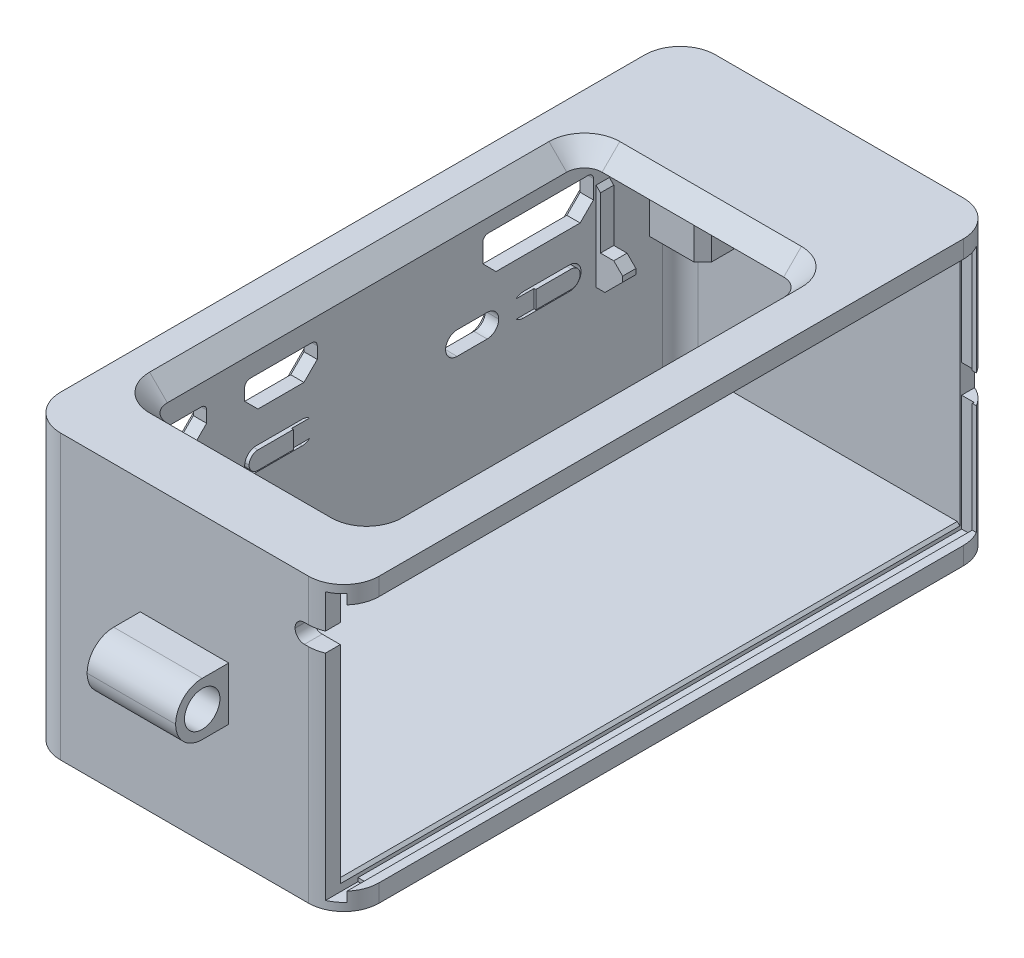
SolidWorks part; units mm, degrees
ref_plane "前视基准面" through (0, 0, 0) normal (0, 0, 1) x (1, 0, 0)
ref_plane "上视基准面" through (0, 0, 0) normal (0, 1, 0) x (1, 0, 0)
ref_plane "右视基准面" through (0, 0, 0) normal (1, 0, 0) x (0, 0, -1)
sketch "草图1" plane through (0, 0, 0) normal (1, 0, 0) x (0, 0, -1)
  line L1 (-54.0501, 29.0398) -> (19.9499, 29.0398)
  line L2 (-54.0501, 29.0398) -> (-54.0501, -2.9602)
  line L3 (-54.0501, -2.9602) -> (19.9499, -2.9602)
  line L4 (19.9499, 29.0398) -> (19.9499, -2.9602)
  dimension "D1" = 74
  dimension "D2" = 32
extrude "凸台-拉伸1" add sketch "草图1" along normal blind 36
sketch "草图2" plane through (36, 0, 0) normal (1, 0, 0) x (0, 0, -1)
  line L8 (17.9499, -0.9602) -> (17.9499, 27.0398)
  line L9 (-52.0501, -0.9602) -> (17.9499, -0.9602)
  line L10 (-52.0501, 27.0398) -> (-52.0501, -0.9602)
  line L11 (17.9499, 27.0398) -> (-52.0501, 27.0398)
  line L12 (17.9499, -0.9602) -> (17.9499, 27.0398)
  line L13 (-52.0501, -0.9602) -> (17.9499, -0.9602)
  line L14 (-52.0501, 27.0398) -> (-52.0501, -0.9602)
  line L15 (17.9499, 27.0398) -> (-52.0501, 27.0398)
  dimension "D1" = 2
extrude "切除-拉伸1" cut sketch "草图2" against normal blind 34
fillet "圆角1" radius 2 2 edges at (2, 13.0398, -17.9499) (2, 13.0398, 52.0501)
fillet "圆角2" radius 4 4 edges at (0, 13.0398, -19.9499) (0, 13.0398, 54.0501) (36, 13.0398, 54.0501) (36, 13.0398, -19.9499)
sketch "草图3" plane through (0, 29.0398, 0) normal (0, 1, 0) x (1, 0, 0)
  line L0 (32, 19.9499) -> (4, 19.9499) construction
  line L1 (29.59, 4.0599) -> (5.07, 4.0599)
  line L2 (29.59, 4.0599) -> (29.59, -45.0601)
  line L3 (29.59, -45.0601) -> (5.07, -45.0601)
  line L4 (5.07, 4.0599) -> (5.07, -45.0601)
  line L5 (36, 15.9499) -> (36, -50.0501) construction
  line L6 (32, -54.0501) -> (4, -54.0501) construction
  line L7 (0, 15.9499) -> (0, -50.0501) construction
  dimension "D1" = 15.89
  dimension "D2" = 6.41
  dimension "D3" = 8.99
  dimension "D4" = 5.07
extrude "切除-拉伸2" cut sketch "草图3" against normal blind 10
fillet "圆角3" radius 2 4 edges at (5.07, 28.0398, 45.0601) (29.59, 28.0398, 45.0601) (29.59, 28.0398, -4.0599) (5.07, 28.0398, -4.0599)
chamfer "倒角1" distance 2 angle 45 8 edges at (17.33, 29.0398, 45.0601) (29.0042, 29.0398, 44.4744) (5.6558, 29.0398, 44.4744) (29.59, 29.0398, 20.5001) (5.07, 29.0398, 20.5001) (29.0042, 29.0398, -3.4741) (5.6558, 29.0398, -3.4741) (17.33, 29.0398, -4.0599)
sketch "草图4" plane through (0, 0, 0) normal (-1, 0, 0) x (0, 0, 1)
  line L0 (-15.9499, 29.0398) -> (50.0501, 29.0398) construction
  line L1 (-8.1499, 22.4398) -> (4.3501, 22.4398)
  line L2 (-8.1499, 22.4398) -> (-8.1499, 18.2398)
  line L3 (-8.1499, 18.2398) -> (4.3501, 18.2398)
  line L4 (4.3501, 22.4398) -> (4.3501, 18.2398)
  line L5 (23.0501, 21.6812) -> (31.2501, 21.6812)
  line L6 (23.0501, 21.6812) -> (23.0501, 18.2398)
  line L7 (23.0501, 18.2398) -> (31.2501, 18.2398)
  line L8 (31.2501, 21.6812) -> (31.2501, 18.2398)
  line L9 (35.5501, 21.6398) -> (43.7501, 21.6398)
  line L10 (35.5501, 21.6398) -> (35.5501, 18.2398)
  line L11 (35.5501, 18.2398) -> (43.7501, 18.2398)
  line L12 (43.7501, 21.6398) -> (43.7501, 18.2398)
  line L13 (-6.7499, 14.7398) -> (1.0501, 14.7398)
  line L14 (-6.7499, 14.7398) -> (-6.7499, 12.1398)
  line L15 (-6.7499, 12.1398) -> (1.0501, 12.1398)
  line L16 (1.0501, 14.7398) -> (1.0501, 12.1398)
  line L17 (23.4501, 14.7398) -> (31.2501, 14.7398)
  line L18 (23.4501, 14.7398) -> (23.4501, 12.1398)
  line L19 (23.4501, 12.1398) -> (31.2501, 12.1398)
  line L20 (31.2501, 14.7398) -> (31.2501, 12.1398)
  line L21 (33.8696, 14.7398) -> (43.3696, 14.7398)
  line L22 (33.8696, 14.7398) -> (33.8696, 11.5398)
  line L23 (33.8696, 11.5398) -> (43.3696, 11.5398)
  line L24 (43.3696, 14.7398) -> (43.3696, 11.5398)
  line L25 (54.0501, 29.0398) -> (54.0501, -2.9602) construction
  line L27 (8.5501, 14.7398) -> (2.5501, 14.7398)
  line L28 (8.5501, 14.7398) -> (8.5501, 12.1398)
  line L29 (8.5501, 12.1398) -> (2.5501, 12.1398)
  line L30 (2.5501, 14.7398) -> (2.5501, 12.1398)
  dimension "D1" = 14.3
  dimension "D2" = 3.2
  dimension "D3" = 2.6
  dimension "D4" = 7.8
  dimension "D5" = 7.8
  dimension "D6" = 8.2
  dimension "D7" = 8.2
  dimension "D8" = 3.4
  dimension "D9" = 12.5
  dimension "D10" = 4.2
  dimension "D11" = 10.8
  dimension "D12" = 10.3
  dimension "D13" = 4.3
  dimension "D14" = 18.7
  dimension "D15" = 9.5
  dimension "D16" = 53
  dimension "D17" = 1.5
  dimension "D18" = 6
extrude "切除-拉伸3" cut sketch "草图4" against normal blind 10
fillet "圆角8" radius 1.3 4 edges at (1, 14.7398, 2.5501) (1, 14.7398, 8.5501) (1, 12.1398, 8.5501) (1, 12.1398, 2.5501)
sketch "草图5" plane through (2, 0, 0) normal (1, 0, 0) x (0, 0, -1)
  line L0 (-23.4501, 12.1398) -> (-23.4501, 14.7398) construction
  line L1 (-23.4501, 14.4398) -> (-30.9501, 14.4398)
  line L2 (-23.4501, 14.4398) -> (-23.4501, 12.4398)
  line L3 (-23.4501, 12.4398) -> (-30.9501, 12.4398)
  line L4 (-30.9501, 14.4398) -> (-30.9501, 12.4398)
  line L5 (-1.0501, 14.7398) -> (-1.0501, 12.1398) construction
  line L6 (-1.0501, 12.4398) -> (6.4499, 12.4398)
  line L7 (-1.0501, 12.4398) -> (-1.0501, 14.4398)
  line L8 (-1.0501, 14.4398) -> (6.4499, 14.4398)
  line L9 (6.4499, 12.4398) -> (6.4499, 14.4398)
  line L10 (-23.4501, 14.7398) -> (-31.2501, 14.7398) construction
  line L11 (-31.2501, 12.1398) -> (-23.4501, 12.1398) construction
  line L12 (-31.2501, 14.7398) -> (-31.2501, 12.1398) construction
  line L13 (6.7499, 14.7398) -> (-1.0501, 14.7398) construction
  line L14 (-1.0501, 12.1398) -> (6.7499, 12.1398) construction
  line L15 (6.7499, 12.1398) -> (6.7499, 14.7398) construction
  dimension "D1" = 0.3
  dimension "D2" = 0.3
  dimension "D3" = 0.3
  dimension "D4" = 0.3
  dimension "D5" = 0.3
  dimension "D6" = 0.3
extrude "凸台-拉伸2" add sketch "草图5" against normal blind 1.2
sketch "草图6" plane through (0.8, 0, 0) normal (-1, 0, 0) x (0, 0, 1)
  line L0 (1.0501, 12.4398) -> (-6.4499, 12.4398) construction
  line L1 (-6.4499, 14.4398) -> (-1.4499, 14.4398)
  line L2 (-6.4499, 14.4398) -> (-6.4499, 12.4398)
  line L3 (-6.4499, 12.4398) -> (-1.4499, 12.4398)
  line L4 (-1.4499, 14.4398) -> (-1.4499, 12.4398)
  line L5 (30.9501, 12.4398) -> (23.4501, 12.4398) construction
  line L6 (30.9501, 14.4398) -> (25.9501, 14.4398)
  line L7 (30.9501, 14.4398) -> (30.9501, 12.4398)
  line L8 (30.9501, 12.4398) -> (25.9501, 12.4398)
  line L9 (25.9501, 14.4398) -> (25.9501, 12.4398)
  dimension "D1" = 5
  dimension "D2" = 5
extrude "凸台-拉伸3" add sketch "草图6" along normal blind 1.5 and the other way blind 1.4
fillet "圆角4" radius 0.6 10 edges at (1, 11.5398, 33.8696) (1, 14.7398, 33.8696) (1, 14.7398, 43.3696) (1, 11.5398, 43.3696) (1, 21.6398, 35.5501) (1, 21.6398, 43.7501) (1, 21.6812, 31.2501) (1, 21.6812, 23.0501) (1, 22.4398, -8.1499) (1, 22.4398, 4.3501)
chamfer "倒角2" distance 1.5 angle 45 6 edges at (1, 18.2398, 43.7501) (1, 18.2398, 35.5501) (1, 18.2398, 31.2501) (1, 18.2398, 23.0501) (1, 18.2398, 4.3501) (1, 18.2398, -8.1499)
fillet "圆角5" radius 1 8 edges at (0.05, 12.4398, 25.9501) (0.05, 14.4398, 25.9501) (0.75, 12.4398, 30.9501) (0.75, 14.4398, 30.9501) (0.05, 12.4398, -1.4499) (0.05, 14.4398, -1.4499) (0.75, 12.4398, -6.4499) (0.75, 14.4398, -6.4499)
chamfer "倒角10" distance 0.2 angle 45 12 edges at (-0.7, 12.4398, 28.4501) (-0.7, 12.7327, 30.6572) (-0.7, 12.7327, 26.243) (-0.7, 14.1469, 30.6572) (-0.7, 14.1469, 26.243) (-0.7, 14.4398, 28.4501) (-0.7, 12.4398, -3.9499) (-0.7, 12.7327, -1.7428) (-0.7, 12.7327, -6.157) (-0.7, 14.1469, -1.7428) (-0.7, 14.1469, -6.157) (-0.7, 14.4398, -3.9499)
fillet "圆角6" radius 1.3 8 edges at (1, 14.7398, 1.0501) (1, 12.1398, 1.0501) (1, 12.1398, -6.7499) (1, 14.7398, -6.7499) (1, 14.7398, 23.4501) (1, 12.1398, 23.4501) (1, 12.1398, 31.2501) (1, 14.7398, 31.2501)
chamfer "倒角4" distance 0.5 angle 45 50 edges at (0, 12.1398, -2.8499) (0, 12.5206, 0.6694) (0, 12.5206, -6.3691) (0, 14.359, 0.6694) (0, 14.359, -6.3691) (0, 14.7398, -2.8499) (0, 18.9898, -7.3999) (0, 18.2398, -1.8999) (0, 18.9898, 3.6001) (0, 20.7898, 4.3501) (0, 20.7898, -8.1499) (0, 22.2641, 4.1744) (0, 22.2641, -7.9741) (0, 22.4398, -1.8999) (0, 11.5398, 38.6196) (0, 11.7155, 43.1938) (0, 11.7155, 34.0453) (0, 13.1398, 43.3696) (0, 13.1398, 33.8696) (0, 14.5641, 43.1938) (0, 14.5641, 34.0453) (0, 14.7398, 38.6196) (0, 12.1398, 27.3501) (0, 12.5206, 30.8694) (0, 12.5206, 23.8309) (0, 14.359, 30.8694) (0, 14.359, 23.8309) (0, 14.7398, 27.3501) (0, 20.4105, 23.0501) (0, 21.5055, 23.2259) (0, 21.6812, 27.1501) (0, 21.5055, 31.0744) (0, 18.9898, 23.8001) (0, 18.2398, 27.1501) (0, 18.9898, 30.5001) (0, 20.4105, 31.2501) (0, 18.9898, 43.0001) (0, 18.2398, 39.6501) (0, 18.9898, 36.3001) (0, 20.3898, 35.5501) (0, 21.4641, 35.7259) (0, 21.6398, 39.6501) (0, 20.3898, 43.7501) (0, 21.4641, 43.5744) (0, 12.5206, 8.1694) (0, 12.1398, 5.5501) (0, 12.5206, 2.9309) (0, 14.359, 8.1694) (0, 14.7398, 5.5501) (0, 14.359, 2.9309)
sketch "草图7" plane through (2, 0, 0) normal (1, 0, 0) x (0, 0, -1)
  line L0 (15.9499, 27.0398) -> (-50.0501, 27.0398) construction
  line L1 (-46.0501, 21.0398) -> (-44.5501, 21.0398)
  line L2 (-46.0501, 21.0398) -> (-46.0501, 11.0398)
  line L3 (-46.0501, 11.0398) -> (-44.5501, 11.0398)
  line L4 (-44.5501, 21.0398) -> (-44.5501, 11.0398)
  line L5 (8.4499, 21.0398) -> (9.9499, 21.0398)
  line L6 (8.4499, 21.0398) -> (8.4499, 11.0398)
  line L7 (8.4499, 11.0398) -> (9.9499, 11.0398)
  line L8 (9.9499, 21.0398) -> (9.9499, 11.0398)
  line L11 (17.9499, -0.9602) -> (17.9499, 27.0398) construction
  line L12 (-52.0501, 27.0398) -> (-52.0501, -0.9602) construction
  dimension "D1" = 6
  dimension "D2" = 10
  dimension "D3" = 1.5
  dimension "D4" = 1.5
  dimension "D5" = 8
  dimension "D6" = 6
extrude "凸台-拉伸4" add sketch "草图7" along normal blind 0.5
sketch "草图10" plane through (2.5, 0, 0) normal (1, 0, 0) x (0, 0, -1)
  line L1 (-46.0501, 11.0398) -> (-44.5501, 11.0398)
  line L2 (-46.0501, 11.0398) -> (-46.0501, 14.6398)
  line L3 (-46.0501, 14.6398) -> (-44.5501, 14.6398)
  line L4 (-44.5501, 11.0398) -> (-44.5501, 14.6398)
  line L7 (8.4499, 11.0398) -> (9.9499, 11.0398)
  line L8 (8.4499, 11.0398) -> (8.4499, 14.6398)
  line L9 (8.4499, 14.6398) -> (9.9499, 14.6398)
  line L10 (9.9499, 11.0398) -> (9.9499, 14.6398)
  dimension "D1" = 3.6
extrude "凸台-拉伸6" add sketch "草图10" along normal blind 2.5
chamfer "倒角7" distance 1 angle 45 2 edges at (5, 14.6398, -9.1999) (5, 14.6398, 45.3001)
chamfer "倒角8" distance 2 angle 45 2 edges at (5, 11.0398, 45.3001) (5, 11.0398, -9.1999)
chamfer "倒角5" distance 0.5 angle 45 2 edges at (2.5, 21.0398, 45.3001) (2.5, 21.0398, -9.1999)
sketch "草图8" plane through (2, 0, 0) normal (1, 0, 0) x (0, 0, -1)
  line L1 (-52.0501, 22.2398) -> (-48.0501, 22.2398)
  line L2 (-52.0501, 22.2398) -> (-52.0501, 24.2398)
  line L3 (-52.0501, 24.2398) -> (-48.0501, 24.2398)
  line L4 (-48.0501, 22.2398) -> (-48.0501, 24.2398)
  line L6 (17.9499, 24.2398) -> (11.9499, 24.2398)
  line L7 (17.9499, 24.2398) -> (17.9499, 22.2398)
  line L8 (17.9499, 22.2398) -> (11.9499, 22.2398)
  line L9 (11.9499, 24.2398) -> (11.9499, 22.2398)
  line L10 (15.9499, 27.0398) -> (-50.0501, 27.0398) construction
  line L11 (17.9499, -0.9602) -> (17.9499, 27.0398) construction
  line L12 (-52.0501, 27.0398) -> (-52.0501, -0.9602) construction
  dimension "D1" = 2.8
  dimension "D2" = 2
  dimension "D3" = 4
  dimension "D4" = 6
extrude "凸台-拉伸5" add sketch "草图8" along normal blind 5
chamfer "倒角6" distance 1 angle 45 2 edges at (7, 24.2398, -14.9499) (7, 24.2398, 50.0501)
sketch "草图12" plane through (0, 0, 54.0501) normal (0, 0, 1) x (1, 0, 0)
  line L0 (4, -0.9602) -> (35.4641, -0.9602) construction
  line L1 (36, 27.0398) -> (33.6, 27.0398)
  line L2 (36, 27.0398) -> (36, -0.9602)
  line L3 (36, -0.9602) -> (33.6, -0.9602)
  line L4 (33.6, 27.0398) -> (33.6, -0.9602)
  dimension "D1" = 2.4
extrude "切除-拉伸5" cut sketch "草图12" against normal blind 10.8
sketch "草图11" plane through (0, -0.9602, 0) normal (0, 1, 0) x (1, 0, 0)
  line L0 (32, 19.9499) -> (4, 19.9499) construction
  line L1 (35, 17.9499) -> (33.6, 17.9499)
  line L2 (35, 17.9499) -> (35, -54.0501)
  line L3 (35, -54.0501) -> (33.6, -54.0501)
  line L4 (33.6, 17.9499) -> (33.6, -54.0501)
  line L5 (32, -54.0501) -> (4, -54.0501) construction
  line L6 (36, -50.0501) -> (36, 15.9499) construction
  dimension "D1" = 2
  dimension "D2" = 0
  dimension "D3" = 1
  dimension "D4" = 1.4
extrude "切除-拉伸4" cut sketch "草图11" against normal blind 0.7
sketch "草图13" plane through (0, 27.0398, 0) normal (0, -1, 0) x (1, 0, 0)
  line L10 (33.6, -17.9499) -> (35, -17.9499)
  line L11 (33.6, 54.0501) -> (33.6, -17.9499)
  line L12 (35, 54.0501) -> (33.6, 54.0501)
  line L13 (35, -17.9499) -> (35, 54.0501)
  line L14 (33.6, -17.9499) -> (35, -17.9499)
  line L15 (33.6, 54.0501) -> (33.6, -17.9499)
  line L16 (35, 54.0501) -> (33.6, 54.0501)
  line L17 (35, -17.9499) -> (35, 54.0501)
  dimension "D1" = 0
extrude "切除-拉伸6" cut sketch "草图13" against normal blind 0.7
sketch "草图14" plane through (0, -1.6602, 0) normal (0, 1, 0) x (1, 0, 0)
  line L1 (33.6, -54.0501) -> (35, -54.0501)
  line L2 (33.6, -54.0501) -> (33.6, -50.0501)
  line L3 (33.6, -50.0501) -> (35, -50.0501)
  line L4 (35, -54.0501) -> (35, -50.0501)
  line L5 (32, -54.0501) -> (4, -54.0501) construction
  line L6 (33.6, -53.7162) -> (33.6, 17.9499) construction
  dimension "D1" = 4
extrude "切除-拉伸7" cut sketch "草图14" against normal blind 0.4
sketch "草图15" plane through (0, 27.7398, 0) normal (0, -1, 0) x (1, 0, 0)
  line L3 (35, 50.0501) -> (35, 52.6959)
  line L4 (33.6, 50.0501) -> (35, 50.0501)
  line L5 (33.6, 53.7162) -> (33.6, 50.0501)
  line L7 (33.6, 50.0501) -> (35, 50.0501)
  line L8 (33.6, 53.7162) -> (33.6, 50.0501)
  line L10 (35, 50.0501) -> (35, 52.6959)
  arc A1 (35, 52.6959) -> (33.6, 53.7162) centre (32, 50.0501) ccw
  arc A2 (35, 52.6959) -> (33.6, 53.7162) centre (32, 50.0501) ccw
  dimension "D1" = 0
extrude "切除-拉伸8" cut sketch "草图15" against normal blind 0.4
sketch "草图16" plane through (0, 0, -17.9499) normal (0, 0, 1) x (1, 0, 0)
  line L0 (33.6, 28.1398) -> (33.6, -2.0602) construction
  line L1 (33.6, 27.7398) -> (35, 27.7398)
  line L2 (33.6, 27.7398) -> (33.6, -1.6602)
  line L3 (33.6, -1.6602) -> (35, -1.6602)
  line L4 (35, 27.7398) -> (35, -1.6602)
extrude "切除-拉伸9" cut sketch "草图16" against normal blind 0.2
chamfer "倒角9" distance 0.3 angle 45 2 edges at (33.6, 27.0398, 17.0501) (33.6, -0.9602, 17.0501)
ref_plane "基准面4" through (0, 13.0398, 0) normal (0, -1, 0) x (-1, 0, 0)
sketch "草图19" plane through (0, 0, -18.1499) normal (0, 0, 1) x (1, 0, 0)
  line L0 (35, 13.0398) -> (40.512, 13.0398) construction
  line L1 (35.4641, -0.9602) -> (35.4641, 27.0398) construction
  line L3 (34.3, 27.7398) -> (34.3, 24.7272) construction
  line L4 (33.6, 27.7398) -> (35, 27.7398) construction
  line L6 (33.6, 14.6398) -> (35.4641, 14.6398)
  line L7 (33.6, 14.6398) -> (33.6, 11.4398)
  line L8 (33.6, 11.4398) -> (35.4641, 11.4398)
  line L9 (35.4641, 14.6398) -> (35.4641, 11.4398)
  line L10 (33.6, 14.6398) -> (35.4641, 11.4398) construction
  line L11 (33.6, 11.4398) -> (35.4641, 14.6398) construction
  point P2 (34.3, 13.0398)
  point P9 (35.4641, 11.1961)
  point P10 (34.5321, 13.0398)
  point P13 (35.4641, 13.0398)
  point P16 (34.3, 27.7398)
  point P17 (35, 14.6366)
  point P18 (0, 0)
  dimension "D1" = 3.2
extrude "切除-拉伸11" cut sketch "草图19" against normal blind 10 and the other way blind 2
sketch "草图20" plane through (0, 0, 54.0501) normal (0, 0, 1) x (1, 0, 0)
  line L0 (33.6, 24.2398) -> (33.6, 28.1198) construction
  line L1 (33.6, 24.2898) -> (30.5, 24.2898)
  line L2 (33.6, 24.2898) -> (33.6, 22.1398)
  line L3 (33.6, 22.1398) -> (30.5, 22.1398)
  line L4 (30.5, 24.2898) -> (30.5, 22.1398)
  line L5 (32, 29.0398) -> (4, 29.0398) construction
  dimension "D1" = 4.75
  dimension "D2" = 2.15
  dimension "D3" = 3.1
extrude "切除-拉伸12" cut sketch "草图20" against normal up to next
fillet "圆角9" radius 1.05 2 edges at (30.5, 24.2898, 53.0501) (30.5, 22.1398, 53.0501)
sketch "草图21" plane through (0, 0, -19.9499) normal (0, 0, -1) x (-1, 0, 0)
  line L0 (-25, 19.5398) -> (-14, 19.5398) construction
  line L1 (-25, 21.0398) -> (-14, 21.0398)
  line L2 (-25, 18.0398) -> (-14, 18.0398)
  line L3 (-4, -2.9602) -> (-4, 29.0398) construction
  line L4 (-32, 29.0398) -> (-4, 29.0398) construction
  arc A0 (-25, 21.0398) -> (-25, 18.0398) centre (-25, 19.5398) ccw
  arc A1 (-14, 18.0398) -> (-14, 21.0398) centre (-14, 19.5398) ccw
  point P2 (-19.5, 19.5398)
  dimension "D4" = 1.5
  dimension "D1" = 10
  dimension "D2" = 9.5
  dimension "D3" = 11
extrude "切除-拉伸13" cut sketch "草图21" against normal up to next
sketch "草图22" plane through (0, -2.9602, 0) normal (0, -1, 0) x (1, 0, 0)
  line L0 (7.07, -6.0599) -> (27.59, -6.0599) construction
  line B0 (12.438, 7.4573) -> (11.965, 6.6368)
  line B1 (11.965, 6.6368) -> (9.5089, 2.3799)
  line B2 (9.5089, 2.3799) -> (9.0302, 1.5593)
  line B3 (9.0302, -0.1617) -> (9.5089, -0.9823)
  line B4 (9.5089, -0.9823) -> (11.965, -5.2392)
  line B5 (11.965, -5.2392) -> (12.438, -6.0599)
  line B6 (13.9253, -6.9204) -> (20.7409, -6.9204)
  line B7 (22.2283, -6.0599) -> (22.7013, -5.2392)
  line B8 (22.7013, -5.2392) -> (25.1574, -0.9823)
  line B9 (25.1574, -0.9823) -> (25.6361, -0.1617)
  line B10 (25.6361, 1.5593) -> (25.1574, 2.3799)
  line B11 (25.1574, 2.3799) -> (22.7013, 6.6368)
  line B12 (22.7013, 6.6368) -> (22.2283, 7.4573)
  line B13 (20.7409, 8.3178) -> (13.9253, 8.3178)
  line B14 (13.1161, -4.9657) -> (10.073, 0.2999)
  line B15 (10.073, 1.1034) -> (13.1218, 6.3404)
  line B16 (13.8228, 6.3461) -> (16.8658, 1.2573)
  line B17 (22.0231, 2.8358) -> (22.3536, 2.2431)
  line B18 (22.4505, 2.1861) -> (24.1601, 2.1861)
  line B19 (24.257, 2.1292) -> (24.8838, 1.0236)
  line B20 (24.787, 0.8583) -> (19.51, 0.8583)
  line B21 (19.4131, 0.9153) -> (18.3475, 2.7959)
  line B22 (21.6698, 6.7393) -> (22.291, 5.6452)
  line B23 (22.1941, 5.4799) -> (19.681, 5.4799)
  line B24 (19.5841, 5.537) -> (18.9686, 6.6311)
  line B25 (19.0655, 6.7963) -> (21.5729, 6.7963)
  line B26 (21.0088, 2.7674) -> (21.2709, 2.2431)
  line B27 (21.1512, 2.1861) -> (19.8064, 2.1861)
  line B28 (19.7095, 2.2431) -> (19.4359, 2.7332)
  line B29 (14.404, 12.3126) -> (14.404, 10.4377)
  line B30 (14.404, 10.4377) -> (20.9689, 10.4377)
  line B31 (20.9689, 10.4377) -> (20.9689, 11.2698)
  line B32 (20.9689, 11.2698) -> (18.3646, 11.2698)
  line B33 (18.3646, 11.2698) -> (18.3646, 12.3582)
  line B34 (17.6921, 12.25) -> (17.6921, 11.2698)
  line B35 (17.6921, 11.2698) -> (15.0765, 11.2698)
  line B36 (15.0765, 11.2698) -> (15.0765, 12.2158)
  line B37 (16.1022, 15.8514) -> (20.9689, 15.8514)
  line B38 (20.9689, 15.8514) -> (20.9689, 16.6665)
  line B39 (20.9689, 16.6665) -> (16.1022, 16.6665)
  line B40 (16.1022, 16.6665) -> (16.1022, 15.8514)
  line B41 (17.1793, 21.3735) -> (16.8487, 20.5415)
  line B42 (16.0623, 21.6983) -> (15.0594, 22.4962)
  line B43 (18.0227, 19.265) -> (18.3817, 20.1141)
  line B44 (19.0313, 18.564) -> (20.1369, 17.658)
  line B45 (15.8743, 26.4795) -> (19.2137, 26.4795)
  line B46 (18.8262, 25.0377) -> (15.8743, 25.0377)
  line B47 (15.8743, 25.0377) -> (15.8743, 23.4478)
  line B48 (15.8743, 23.4478) -> (19.0256, 23.4478)
  line B49 (20.2679, 26.6277) -> (20.2679, 26.6618)
  line B50 (20.2679, 26.6618) -> (20.9689, 26.7759)
  line B51 (20.9689, 26.7759) -> (20.9689, 28.0751)
  line B52 (20.9689, 28.0751) -> (15.8743, 28.0751)
  line B53 (15.8743, 28.0751) -> (15.8743, 26.4795)
  line B54 (19.9659, 31.9274) -> (19.9659, 31.1239)
  line B55 (17.0254, 33.0216) -> (17.0254, 33.8079)
  line B56 (17.0254, 33.8079) -> (15.8743, 33.8079)
  line B57 (15.8743, 33.8079) -> (15.8743, 31.9388)
  line B58 (18.9174, 29.6878) -> (18.9516, 29.6878)
  line B59 (20.7808, 29.591) -> (20.8264, 29.591)
  line B60 (21.1854, 31.141) -> (21.1854, 31.6254)
  line B61 (16.4156, 34.2638) -> (17.4642, 34.8223)
  line B62 (20.456, 37.0676) -> (20.456, 37.1075)
  line B63 (20.456, 37.1075) -> (20.9689, 37.2214)
  line B64 (20.9689, 37.2214) -> (20.9689, 38.5207)
  line B65 (20.9689, 38.5207) -> (18.074, 38.5207)
  line B66 (18.6381, 36.9251) -> (19.453, 36.9251)
  line B67 (16.7576, 41.0111) -> (16.7576, 40.9769)
  line B68 (16.7576, 40.9769) -> (15.8743, 40.8686)
  line B69 (15.8743, 40.8686) -> (15.8743, 39.5693)
  line B70 (15.8743, 39.5693) -> (20.9689, 39.5693)
  line B71 (20.9689, 39.5693) -> (20.9689, 41.1536)
  line B72 (20.9689, 41.1536) -> (18.0569, 41.1536)
  line B73 (17.2248, 42.8118) -> (15.8515, 43.0796)
  line B74 (21.2709, 2.2431) -> (22.3536, 2.2431)
  line B75 (21.1512, 2.1861) -> (22.4505, 2.1861)
  spline B76 degree 3 poles (9.0302, 1.5593) (8.882, 1.2914) (8.8022, 0.9951) (8.8022, 0.6988) knots 3 3 3 3 4 4 4 4
  spline B77 degree 3 poles (8.8022, 0.6988) (8.8022, 0.4025) (8.882, 0.1061) (9.0302, -0.1617) knots 4 4 4 4 5 5 5 5
  spline B78 degree 3 poles (12.438, -6.0599) (12.7457, -6.5898) (13.3156, -6.9204) (13.9253, -6.9204) knots 8 8 8 8 9 9 9 9
  spline B79 degree 3 poles (20.7409, -6.9204) (21.3564, -6.9204) (21.9206, -6.5898) (22.2283, -6.0599) knots 10 10 10 10 11 11 11 11
  spline B80 degree 3 poles (25.6361, -0.1617) (25.7899, 0.1061) (25.864, 0.4025) (25.864, 0.6988) knots 14 14 14 14 15 15 15 15
  spline B81 degree 3 poles (25.864, 0.6988) (25.864, 0.9951) (25.7899, 1.2914) (25.6361, 1.5593) knots 15 15 15 15 16 16 16 16
  spline B82 degree 3 poles (22.2283, 7.4573) (21.9206, 7.993) (21.3564, 8.3178) (20.7409, 8.3178) knots 19 19 19 19 20 20 20 20
  spline B83 degree 3 poles (13.9253, 8.3178) (13.3156, 8.3178) (12.7457, 7.993) (12.438, 7.4573) knots 21 21 21 21 22 22 22 22
  spline B84 degree 2 poles (16.8658, 0.146) (13.8911, -5.0056) (13.8854, -5.017) knots 0 0 0 1 1 1
  spline B85 degree 3 poles (13.8854, -5.017) (13.6917, -5.2848) (13.2814, -5.2563) (13.1161, -4.9657) knots 1 1 1 1 2 2 2 2
  spline B86 degree 3 poles (10.073, 0.2999) (9.9306, 0.5449) (9.9306, 0.8527) (10.073, 1.1034) knots 3 3 3 3 4 4 4 4
  spline B87 degree 3 poles (13.1218, 6.3404) (13.2757, 6.6082) (13.6632, 6.6139) (13.8228, 6.3461) knots 5 5 5 5 6 6 6 6
  spline B88 degree 3 poles (16.8658, 1.2573) (17.0653, 0.9153) (17.0653, 0.4879) (16.8658, 0.146) knots 7 7 7 7 8 8 8 8
  spline B89 degree 3 poles (24.1601, 2.1861) (24.2, 2.1861) (24.2342, 2.169) (24.257, 2.1292) knots 3 3 3 3 4 4 4 4
  spline B90 degree 3 poles (24.8838, 1.0236) (24.9237, 0.9495) (24.8725, 0.8583) (24.787, 0.8583) knots 5 5 5 5 6 6 6 6
  spline B91 degree 3 poles (19.51, 0.8583) (19.4701, 0.8583) (19.4302, 0.8754) (19.4131, 0.9153) knots 7 7 7 7 8 8 8 8
  spline B92 degree 3 poles (18.3475, 2.7959) (17.6579, 4.0154) (17.5212, 5.024) (18.8889, 5.024) knots 9 9 9 9 10 10 10 10
  spline B93 degree 3 poles (18.8889, 5.024) (20.2053, 5.024) (21.3621, 4.004) (22.0231, 2.8358) knots 10 10 10 10 11 11 11 11
  spline B94 degree 3 poles (21.5729, 6.7963) (21.6128, 6.7963) (21.6527, 6.7735) (21.6698, 6.7393) knots 0 0 0 0 1 1 1 1
  spline B95 degree 3 poles (22.291, 5.6452) (22.3309, 5.5711) (22.2795, 5.4799) (22.1941, 5.4799) knots 2 2 2 2 3 3 3 3
  spline B96 degree 3 poles (19.681, 5.4799) (19.6411, 5.4799) (19.6069, 5.5027) (19.5841, 5.537) knots 4 4 4 4 5 5 5 5
  spline B97 degree 3 poles (18.9686, 6.6311) (18.9288, 6.7051) (18.98, 6.7963) (19.0655, 6.7963) knots 6 6 6 6 7 7 7 7
  spline B98 degree 3 poles (17.2989, 6.141) (17.0482, 6.5798) (17.1565, 6.8932) (17.5554, 6.8932) (17.9486, 6.8932) (18.4102, 6.5798) (18.6552, 6.141) knots 2 2 2 2 3 3 3 4 4 4 4
  spline B99 degree 3 poles (18.6552, 6.141) (18.9117, 5.6965) (18.8034, 5.3831) (18.4102, 5.3831) (18.0056, 5.3831) (17.5497, 5.6965) (17.2989, 6.141) knots 0 0 0 0 1 1 1 2 2 2 2
  spline B100 degree 3 poles (19.624, 3.7248) (20.1654, 3.7248) (20.644, 3.4171) (21.0088, 2.7674) knots 0 0 0 0 1 1 1 1
  spline B101 degree 3 poles (19.8064, 2.1861) (19.7665, 2.1861) (19.7266, 2.2089) (19.7095, 2.2431) knots 4 4 4 4 5 5 5 5
  spline B102 degree 3 poles (19.4359, 2.7332) (19.0712, 3.3714) (19.0655, 3.7248) (19.624, 3.7248) knots 6 6 6 6 7 7 7 7
  spline B103 degree 3 poles (18.3646, 12.3582) (18.3646, 13.7886) (17.715, 14.7745) (16.3302, 14.7745) knots 5 5 5 5 6 6 6 6
  spline B104 degree 3 poles (16.3302, 14.7745) (14.8941, 14.7745) (14.404, 13.7886) (14.404, 12.3126) knots 6 6 6 6 7 7 7 7
  spline B105 degree 3 poles (15.0765, 12.2158) (15.0765, 13.3669) (15.3785, 13.9482) (16.3302, 13.9482) knots 3 3 3 3 4 4 4 4
  spline B106 degree 3 poles (16.3302, 13.9482) (17.2704, 13.9482) (17.6921, 13.4068) (17.6921, 12.25) knots 4 4 4 4 5 5 5 5
  spline B107 degree 3 poles (15.0993, 16.2618) (15.0993, 16.5866) (14.877, 16.826) (14.575, 16.826) (14.2388, 16.826) (14.045, 16.5866) (14.045, 16.2618) knots 2 2 2 2 3 3 3 4 4 4 4
  spline B108 degree 3 poles (14.045, 16.2618) (14.045, 15.937) (14.2388, 15.6976) (14.575, 15.6976) (14.877, 15.6976) (15.0993, 15.937) (15.0993, 16.2618) knots 0 0 0 0 1 1 1 2 2 2 2
  spline B109 degree 3 poles (16.8487, 20.5415) (16.6151, 19.9545) (16.4726, 19.5328) (16.1022, 19.5328) knots 1 1 1 1 2 2 2 2
  spline B110 degree 3 poles (16.1022, 19.5328) (15.7489, 19.5328) (15.5494, 19.8349) (15.5494, 20.3306) knots 2 2 2 2 3 3 3 3
  spline B111 degree 3 poles (15.5494, 20.3306) (15.5494, 20.8492) (15.7261, 21.2595) (16.0623, 21.6983) knots 3 3 3 3 4 4 4 4
  spline B112 degree 3 poles (15.0594, 22.4962) (14.4724, 21.9149) (14.1761, 21.1) (14.1761, 20.3306) knots 5 5 5 5 6 6 6 6
  spline B113 degree 3 poles (14.1761, 20.3306) (14.1761, 18.9117) (15.0765, 17.9087) (16.1934, 17.9087) knots 6 6 6 6 7 7 7 7
  spline B114 degree 3 poles (16.1934, 17.9087) (17.1622, 17.9087) (17.7434, 18.564) (18.0227, 19.265) knots 7 7 7 7 8 8 8 8
  spline B115 degree 3 poles (18.3817, 20.1141) (18.621, 20.684) (18.7464, 21.0544) (19.1339, 21.0544) knots 9 9 9 9 10 10 10 10
  spline B116 degree 3 poles (19.1339, 21.0544) (19.4929, 21.0544) (19.7152, 20.7752) (19.7152, 20.1825) knots 10 10 10 10 11 11 11 11
  spline B117 degree 3 poles (19.7152, 20.1825) (19.7152, 19.6582) (19.4359, 19.037) (19.0313, 18.564) knots 11 11 11 11 12 12 12 12
  spline B118 degree 3 poles (20.1369, 17.658) (20.7694, 18.3475) (21.0943, 19.282) (21.0943, 20.1483) knots 13 13 13 13 14 14 14 14
  spline B119 degree 3 poles (21.0943, 20.1483) (21.0943, 21.761) (20.1198, 22.6955) (19.0085, 22.6955) knots 14 14 14 14 15 15 15 15
  spline B120 degree 3 poles (19.0085, 22.6955) (18.0683, 22.6955) (17.5098, 22.1998) (17.1793, 21.3735) knots 15 15 15 15 16 16 16 16
  spline B121 degree 3 poles (19.2137, 26.4795) (19.5898, 26.2117) (19.7323, 25.9894) (19.7323, 25.6304) knots 1 1 1 1 2 2 2 2
  spline B122 degree 3 poles (19.7323, 25.6304) (19.7323, 25.2258) (19.5328, 25.0377) (18.8262, 25.0377) knots 2 2 2 2 3 3 3 3
  spline B123 degree 3 poles (19.0256, 23.4478) (20.2964, 23.4478) (21.0943, 23.9208) (21.0943, 25.032) knots 6 6 6 6 7 7 7 7
  spline B124 degree 3 poles (21.0943, 25.032) (21.0943, 25.7273) (20.7694, 26.206) (20.2679, 26.6277) knots 7 7 7 7 8 8 8 8
  spline B125 degree 3 poles (19.9659, 31.1239) (19.9659, 30.5768) (19.8576, 30.3717) (19.624, 30.3717) knots 1 1 1 1 2 2 2 2
  spline B126 degree 3 poles (19.624, 30.3717) (19.453, 30.3717) (19.3732, 30.4115) (19.265, 30.5312) knots 2 2 2 2 3 3 3 3
  spline B127 degree 3 poles (19.265, 30.5312) (19.3276, 30.7535) (19.3562, 30.9586) (19.3562, 31.1296) knots 3 3 3 3 4 4 4 4
  spline B128 degree 3 poles (19.3562, 31.1296) (19.3562, 32.2579) (18.8376, 33.164) (17.6466, 33.164) knots 4 4 4 4 5 5 5 5
  spline B129 degree 3 poles (17.6466, 33.164) (17.4015, 33.164) (17.1679, 33.1013) (17.0254, 33.0216) knots 5 5 5 5 6 6 6 6
  spline B130 degree 3 poles (15.8743, 31.9388) (15.7888, 31.7051) (15.7489, 31.4259) (15.7489, 31.1296) knots 9 9 9 9 10 10 10 10
  spline B131 degree 3 poles (15.7489, 31.1296) (15.7489, 30.0298) (16.353, 28.9983) (17.601, 28.9983) knots 10 10 10 10 11 11 11 11
  spline B132 degree 3 poles (17.601, 28.9983) (18.1936, 28.9983) (18.6666, 29.3288) (18.9174, 29.6878) knots 11 11 11 11 12 12 12 12
  spline B133 degree 3 poles (18.9516, 29.6878) (19.1852, 29.3573) (19.5442, 29.1236) (19.9032, 29.1236) knots 13 13 13 13 14 14 14 14
  spline B134 degree 3 poles (19.9032, 29.1236) (20.3306, 29.1236) (20.5985, 29.3231) (20.7808, 29.591) knots 14 14 14 14 15 15 15 15
  spline B135 degree 3 poles (20.8264, 29.591) (21.0658, 29.1179) (21.4077, 28.8672) (21.8294, 28.8672) knots 16 16 16 16 17 17 17 17
  spline B136 degree 3 poles (21.8294, 28.8672) (22.7411, 28.8672) (23.1116, 29.8303) (23.1116, 31.0042) knots 17 17 17 17 18 18 18 18
  spline B137 degree 3 poles (23.1116, 31.0042) (23.1116, 32.7765) (22.348, 33.8878) (21.2709, 33.8878) knots 18 18 18 18 19 19 19 19
  spline B138 degree 3 poles (21.2709, 33.8878) (20.3477, 33.8878) (19.9659, 33.1811) (19.9659, 31.9274) knots 19 19 19 19 20 20 20 20
  spline B139 degree 3 poles (18.3988, 31.1296) (18.3988, 30.7649) (18.1309, 30.4857) (17.601, 30.4857) (17.0824, 30.4857) (16.8146, 30.7649) (16.8146, 31.1296) knots 2 2 2 2 3 3 3 4 4 4 4
  spline B140 degree 3 poles (16.8146, 31.1296) (16.8146, 31.5057) (17.0824, 31.7735) (17.601, 31.7735) (18.1309, 31.7735) (18.3988, 31.5057) (18.3988, 31.1296) knots 0 0 0 0 1 1 1 2 2 2 2
  spline B141 degree 3 poles (22.1143, 31.2549) (22.1143, 30.5996) (21.9376, 30.1722) (21.5786, 30.1722) knots 0 0 0 0 1 1 1 1
  spline B142 degree 3 poles (21.5786, 30.1722) (21.4077, 30.1722) (21.2652, 30.252) (21.1227, 30.4115) knots 1 1 1 1 2 2 2 2
  spline B143 degree 3 poles (21.1227, 30.4115) (21.1683, 30.5768) (21.1854, 30.7706) (21.1854, 31.141) knots 2 2 2 2 3 3 3 3
  spline B144 degree 3 poles (21.1854, 31.6254) (21.1854, 32.0983) (21.2481, 32.3662) (21.5501, 32.3662) knots 4 4 4 4 5 5 5 5
  spline B145 degree 3 poles (21.5501, 32.3662) (21.875, 32.3662) (22.1143, 31.9104) (22.1143, 31.2549) knots 5 5 5 5 6 6 6 6
  spline B146 degree 3 poles (15.7489, 36.4579) (15.7489, 35.6657) (16.0167, 34.9363) (16.4156, 34.2638) knots 0 0 0 0 1 1 1 1
  spline B147 degree 3 poles (17.4642, 34.8223) (17.1793, 35.3296) (17.0197, 35.7512) (17.0197, 36.1558) knots 2 2 2 2 3 3 3 3
  spline B148 degree 3 poles (17.0197, 36.1558) (17.0197, 36.6744) (17.259, 36.891) (17.6694, 36.9251) knots 3 3 3 3 4 4 4 4
  spline B149 degree 3 poles (17.6694, 36.9251) (17.8859, 34.9363) (18.4671, 34.0928) (19.5442, 34.0928) knots 4 4 4 4 5 5 5 5
  spline B150 degree 3 poles (19.5442, 34.0928) (20.3933, 34.0928) (21.0943, 34.6684) (21.0943, 35.6088) knots 5 5 5 5 6 6 6 6
  spline B151 degree 3 poles (21.0943, 35.6088) (21.0943, 36.1729) (20.8321, 36.6459) (20.456, 37.0676) knots 6 6 6 6 7 7 7 7
  spline B152 degree 3 poles (18.074, 38.5207) (16.4783, 38.5207) (15.7489, 37.7742) (15.7489, 36.4579) knots 11 11 11 11 12 12 12 12
  spline B153 degree 3 poles (19.453, 36.9251) (19.7038, 36.6915) (19.8576, 36.4806) (19.8576, 36.1558) knots 0 0 0 0 1 1 1 1
  spline B154 degree 3 poles (19.8576, 36.1558) (19.8576, 35.8253) (19.7152, 35.6088) (19.4188, 35.6088) knots 1 1 1 1 2 2 2 2
  spline B155 degree 3 poles (19.4188, 35.6088) (19.0598, 35.6088) (18.7749, 35.9336) (18.6381, 36.9251) knots 2 2 2 2 3 3 3 3
  spline B156 degree 3 poles (15.7489, 42.4642) (15.7489, 41.9513) (16.0794, 41.3872) (16.7576, 41.0111) knots 0 0 0 0 1 1 1 1
  spline B157 degree 3 poles (18.0569, 41.1536) (17.3844, 41.4214) (17.1451, 41.8773) (17.1451, 42.2534) knots 7 7 7 7 8 8 8 8
  spline B158 degree 3 poles (17.1451, 42.2534) (17.1451, 42.4813) (17.1793, 42.6295) (17.2248, 42.8118) knots 8 8 8 8 9 9 9 9
  spline B159 degree 3 poles (15.8515, 43.0796) (15.7888, 42.9372) (15.7489, 42.7663) (15.7489, 42.4642) knots 10 10 10 10 11 11 11 11
sketch_block_instance "块1-1"
sketch_block "块1"
extrude "切除-拉伸14" cut sketch "草图22" against normal blind 0.3
ref_plane "基准面5" through (13, 0, 0) normal (1, 0, 0) x (0, 0, -1)
sketch "草图23" plane through (13, 0, 0) normal (1, 0, 0) x (0, 0, -1)
  line L0 (-54.0501, -2.9602) -> (-54.0501, 22.1398) construction
  line L1 (-54.0501, 16.0398) -> (-60.0501, 16.0398)
  line L2 (-54.0501, 16.0398) -> (-54.0501, 10.0398)
  line L3 (-54.0501, 10.0398) -> (-60.0501, 10.0398)
  line L4 (-60.0501, 16.0398) -> (-60.0501, 10.0398)
  dimension "D1" = 13
  dimension "D2" = 6
  dimension "D3" = 6
extrude "凸台-拉伸7" add sketch "草图23" along normal blind 10
sketch "草图24" plane through (23, 0, 0) normal (1, 0, 0) x (0, 0, -1)
  line L0 (-60.0501, 16.0398) -> (-54.0501, 10.0398) construction
  line L2 (-54.0501, -2.9602) -> (-54.0501, 22.1398) construction
  line L3 (-54.0501, 16.0398) -> (-60.0501, 16.0398) construction
  line L4 (-54.0501, 16.0398) -> (-60.0501, 10.0398) construction
  circle A0 centre (-57.0501, 13.0398) radius 2
  dimension "D1" = 4
extrude "切除-拉伸15" cut sketch "草图24" against normal through all
fillet "圆角10" radius 3 2 edges at (18, 10.0398, 60.0501) (18, 16.0398, 60.0501)
ref_plane "基准面6" through (0, 15, 0) normal (0, 1, 0) x (1, 0, 0)
sketch "草图25" plane through (0, 15, 0) normal (0, 1, 0) x (1, 0, 0)
  line L0 (8, 14.4999) -> (8, 19.1472)
  line L1 (0, -50.0501) -> (0, 15.9499) construction
  line L2 (0, 15.9499) -> (0, -50.0501) construction
  line L3 (1, 14.4999) -> (1, 17.0058)
  line L4 (32, 19.9499) -> (4, 19.9499) construction
  line L5 (1, 17.0058) -> (3.1414, 19.1472)
  line L7 (8, 14.4999) -> (1, 14.4999)
  line L8 (3.1414, 19.1472) -> (8, 19.1472)
  line L9 (8, -50.5366) -> (1, -50.5366)
  line L11 (1, -50.5366) -> (3.1414, -52.9483)
  line L12 (3.1414, -52.9483) -> (8, -52.9483)
  line L13 (8, -52.9483) -> (8, -50.5366)
  point P4 (0, 0)
  point P14 (0, 0)
  point P15 (3.3115, -52.9483)
  point P16 (1.1701, -50.5366)
  point P19 (0, 0)
  dimension "D1" = 8
  dimension "D2" = 5.45
  dimension "D3" = 1
extrude "凸台-拉伸8" add sketch "草图25" along normal blind 5 and the other way blind 2
chamfer "倒角11" distance 1 angle 45 2 edges at (8, 16.5, 50.5366) (8, 16.5, -14.4999)
